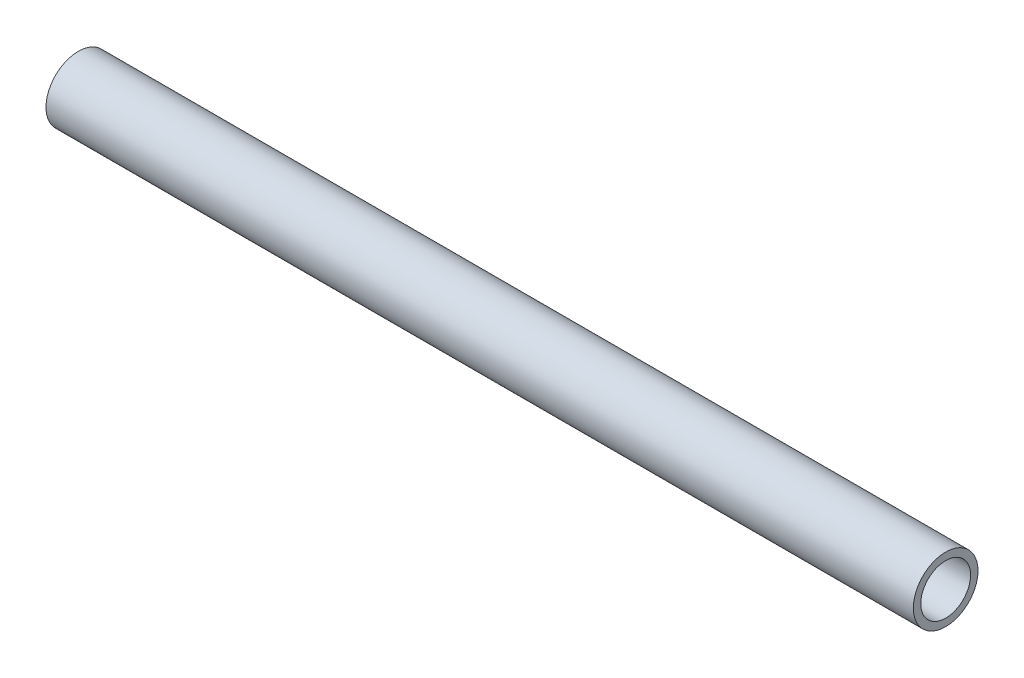
SolidWorks part; units mm, degrees
ref_plane "Front" through (0, 0, 0) normal (0, 0, 1) x (1, 0, 0)
ref_plane "Top" through (0, 0, 0) normal (0, 1, 0) x (1, 0, 0)
ref_plane "Right" through (0, 0, 0) normal (1, 0, 0) x (0, 0, -1)
ref_axis "side-side" through (80.9, 0, 0) along (-1, 0, 0)
ref_axis "up-down" through (0, 50, 0) along (0, -1, 0)
ref_axis "front-back" through (0, 0, -80.9) along (0, 0, 1)
sketch "Sketch1" plane through (0, 0, 0) normal (0, 0, 1) x (1, 0, 0)
  line L4 (-140, 6.604) -> (-140, 8.5725)
  line L5 (89.8802, 6.604) -> (89.8802, 8.5725)
  line L6 (79.7202, 6.2357) -> (-129.84, 6.2357)
  line L7 (89.8802, 8.5725) -> (-140, 8.5725)
  line L9 (89.8802, 6.604) -> (79.7202, 6.604)
  line L10 (-110.2297, 0) -> (138.3106, 0) construction
  line L11 (80.9, 0) -> (-80.9, 0) construction
  line L12 (79.7202, 6.604) -> (79.7202, 6.2357)
  line L14 (91.2802, 14.6769) -> (91.2802, -13.1377) construction
  line L16 (0, -50) -> (0, 50) construction
  line L20 (-140, 6.604) -> (-129.84, 6.604)
  line L21 (-129.84, 6.2357) -> (-129.84, 6.604)
  dimension "D1" = 13.208
  dimension "D2" = 12.4714
  dimension "D3" = 17.145
  dimension "D4" = 1.4
  dimension "D5" = 10.16
  dimension "D6" = 91.2802
  dimension "D7" = 140
revolve "Revolve1" add sketch "Sketch1" angle 360 about L10
